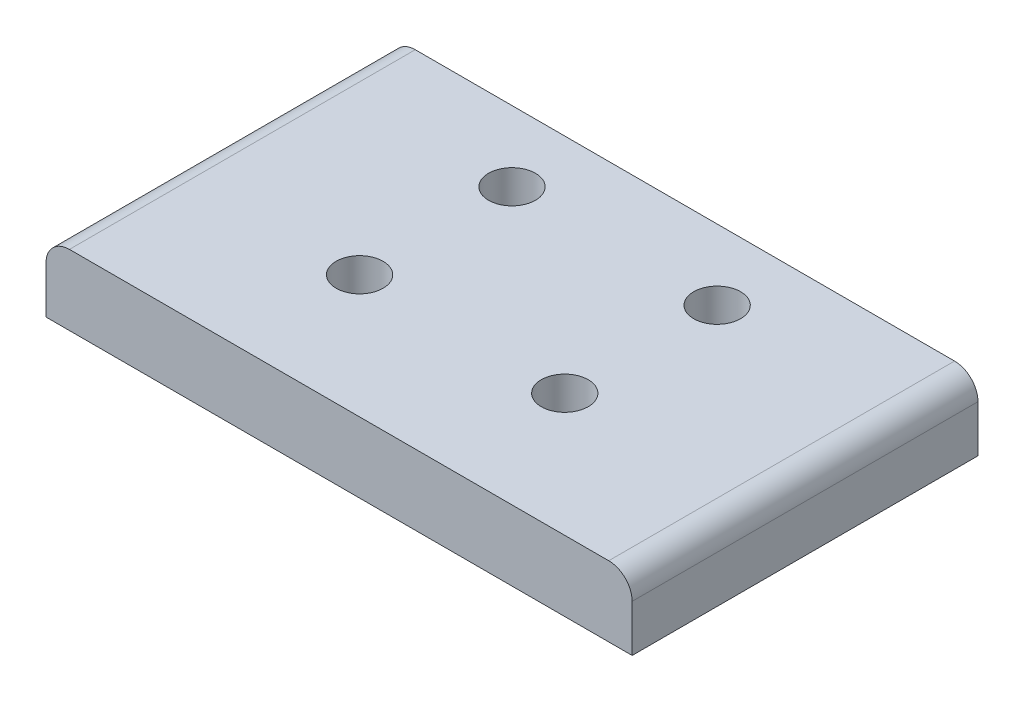
SolidWorks part; units mm, degrees
ref_plane "Front Plane" through (0, 0, 0) normal (0, 0, 1) x (1, 0, 0)
ref_plane "Top Plane" through (0, 0, 0) normal (0, 1, 0) x (1, 0, 0)
ref_plane "Right Plane" through (0, 0, 0) normal (1, 0, 0) x (0, 0, -1)
sketch "Sketch1" plane through (0, 0, 0) normal (0, 1, 0) x (1, 0, 0)
  line L0 (16.25, 0) -> (16.25, 29.5)
  line L1 (0, 0) -> (50, 0)
  line L2 (0, 0) -> (0, 29.5)
  line L3 (0, 29.5) -> (50, 29.5)
  line L4 (50, 0) -> (50, 29.5)
  line L5 (16.25, 10.5) -> (50, 10.5)
  line L6 (33.75, 0) -> (33.75, 29.5)
  line L7 (16.25, 23.5) -> (50, 23.5)
  dimension "D1" = 50
  dimension "D2" = 29.5
  dimension "D3" = 13
  dimension "D4" = 10.5
  dimension "D5" = 17.5
  dimension "D6" = 16.25
extrude "Boss-Extrude1" add sketch "Sketch1" along normal blind 6 contours L3 L2 L1 L0 | L0 L7 L6 L3 | L7 L0 L5 L6 | L7 L6 L5 L4 | L1 L6 L5 L0 | L6 L1 L4 L5 | L6 L7 L4 L3 region at (8.125, 0, -14.75) region at (25, 0, -5.25) region at (25, 0, -17) region at (41.875, 0, -5.25) region at (25, 0, -26.5) region at (41.875, 0, -17) region at (41.875, 0, -26.5)
fillet "Fillet1" radius 2 1 edges at (0, 6, -14.75)
fillet "Fillet2" radius 2 1 edges at (50, 6, -14.75)
sketch "Sketch4" plane through (0, 0, 0) normal (0, -1, 0) x (1, 0, 0)
  line L0 (33.75, 0) -> (33.75, -29.5) construction
  line L1 (16.25, -23.5) -> (33.75, -23.5)
  line L2 (16.25, -23.5) -> (16.25, -10.5)
  line L3 (16.25, -10.5) -> (33.75, -10.5)
  line L4 (33.75, -23.5) -> (33.75, -10.5)
  line L5 (16.25, -10.5) -> (50, -10.5) construction
  dimension "D1" = 0
  dimension "D2" = 0
hole_wizard "Ø4.0mm Dowel Hole2" positions "3DSketch3" profile "Sketch5" hole size "Ø4.0" standard "ANSI Metric" end condition through all
sketch3d "3DSketch3"
  point P0 (16.25, 0, -23.5)
  point P3 (33.75, 0, -23.5)
  point P6 (33.75, 0, -10.5)
  point P9 (16.25, 0, -10.5)
sketch "Sketch5" plane through (16.25, 0, -23.5) normal (1, 0, 0) x (0, 0, -1)
  line L0 (0, 0) -> (0, 6)
  line L1 (0, 6) -> (2, 6)
  line L2 (2, 6) -> (2, 0)
  line L5 (2, 0) -> (0, 0)
  line L11 (0, -6.35) -> (0, 107.95) construction
  dimension "Thru Hole Dia." = 4
  dimension "Thru Hole Depth" = 6
